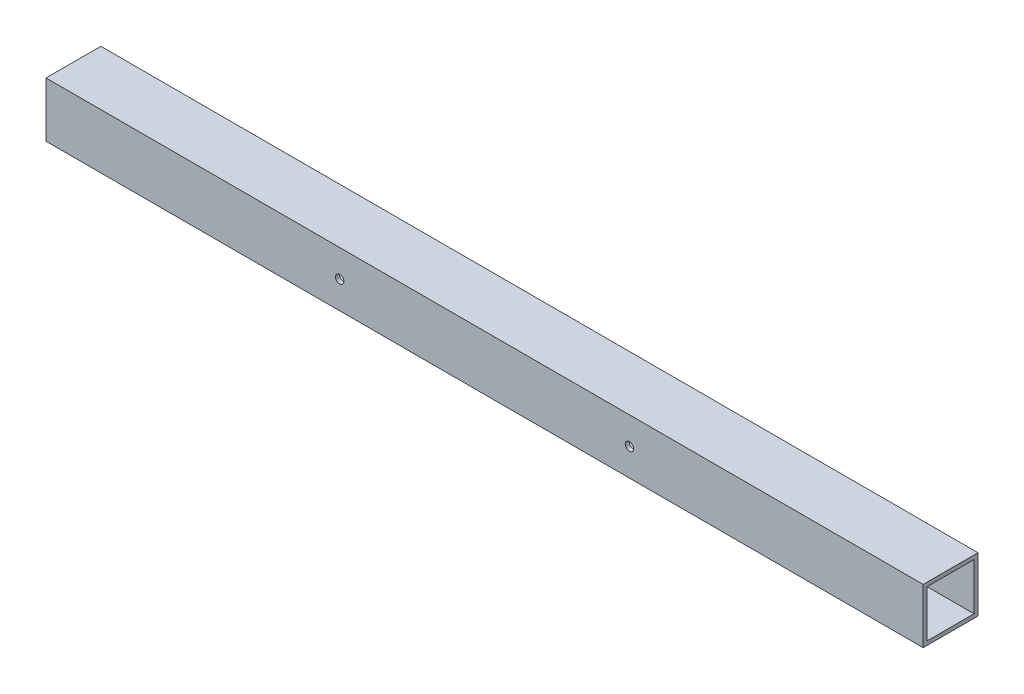
SolidWorks part; units mm, degrees
material "6061-T6 (SS)"
ref_plane "Front Plane" through (0, 0, 0) normal (0, 0, 1) x (1, 0, 0)
ref_plane "Top Plane" through (0, 0, 0) normal (0, 1, 0) x (1, 0, 0)
ref_plane "Right Plane" through (0, 0, 0) normal (1, 0, 0) x (0, 0, -1)
sketch "Sketch1" plane through (0, 0, 0) normal (1, 0, 0) x (0, 0, -1)
  line L1 (-22.225, -22.225) -> (22.225, -22.225)
  line L2 (-22.225, -22.225) -> (-22.225, 22.225)
  line L3 (-22.225, 22.225) -> (22.225, 22.225)
  line L4 (22.225, -22.225) -> (22.225, 22.225)
  line L5 (-22.225, -22.225) -> (22.225, 22.225) construction
  line L6 (-22.225, 22.225) -> (22.225, -22.225) construction
  line L7 (-19.05, -19.05) -> (19.05, -19.05)
  line L8 (-19.05, -19.05) -> (-19.05, 19.05)
  line L9 (-19.05, 19.05) -> (19.05, 19.05)
  line L10 (19.05, -19.05) -> (19.05, 19.05)
  line L11 (-19.05, -19.05) -> (19.05, 19.05) construction
  line L12 (-19.05, 19.05) -> (19.05, -19.05) construction
  point P0 (0, 0)
  point P6 (0, 0)
  dimension "D1" = 44.45
  dimension "D2" = 3.175
extrude "Boss-Extrude1" add sketch "Sketch1" along normal blind 355.6 and the other way blind 355.6
hole_wizard "17/64 (0.26563) Diameter Hole1" positions "Sketch6" profile "Sketch7" hole size "17/64" standard "ANSI Inch" end condition through all
sketch "Sketch6" plane through (0, 0, 22.225) normal (0, 0, 1) x (1, 0, 0)
  point P0 (-117.475, 0)
  point P5 (117.475, 0)
  dimension "D1" = 234.95
  dimension "D2" = 117.475
sketch "Sketch7" plane through (-117.475, 0, 22.225) normal (1, 0, 0) x (0, -1, 0)
  line L0 (0, 0) -> (0, 44.45)
  line L1 (0, 44.45) -> (3.3735, 44.45)
  line L2 (3.3735, 44.45) -> (3.3735, 0)
  line L5 (3.3735, 0) -> (0, 0)
  line L11 (0, -6.35) -> (0, 107.95) construction
  dimension "Thru Hole Dia." = 6.747
  dimension "Thru Hole Depth" = 44.45
